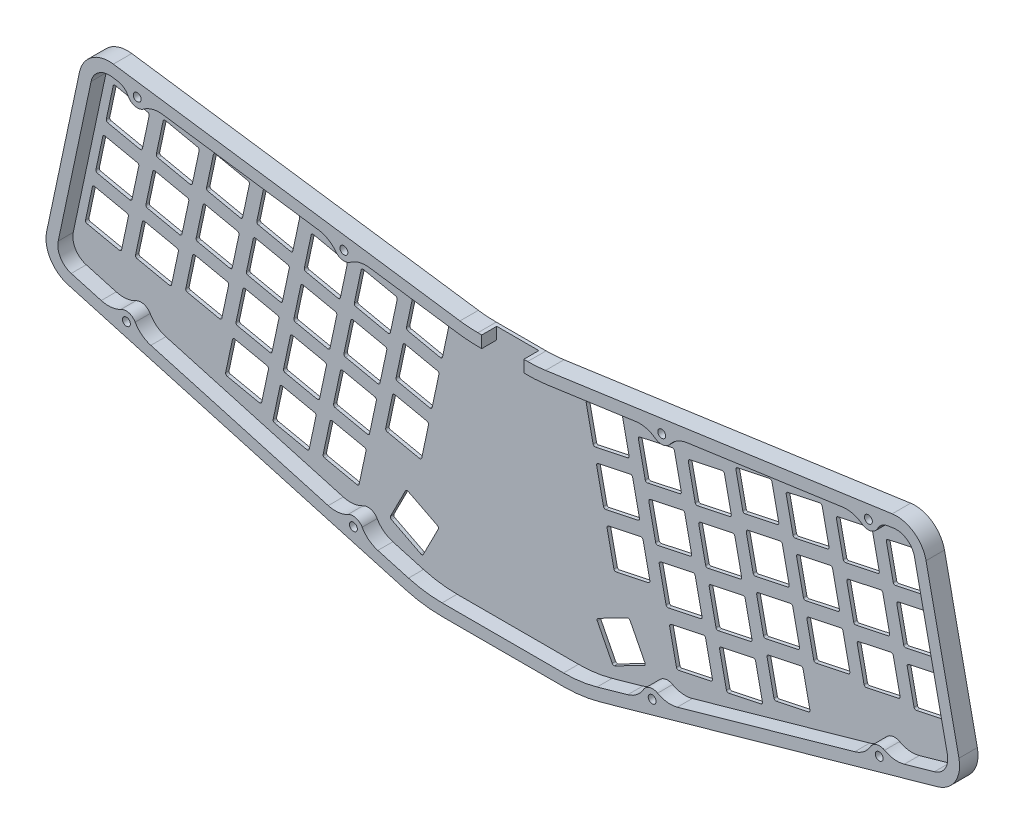
SolidWorks part; units mm, degrees
ref_plane "Front Plane" through (0, 0, 0) normal (0, 0, 1) x (1, 0, 0)
ref_plane "Top Plane" through (0, 0, 0) normal (0, 1, 0) x (1, 0, 0)
ref_plane "Right Plane" through (0, 0, 0) normal (1, 0, 0) x (0, 0, -1)
sketch "Model" plane through (0, 0, 0) normal (0, 0, 1) x (1, 0, 0)
  line L0 (7.1929, 63.9009) -> (19.4198, 61.302)
  line L1 (19.9974, 60.4125) -> (17.3986, 48.1856)
  line L2 (16.509, 47.6079) -> (4.2822, 50.2068)
  line L3 (3.7045, 51.0964) -> (6.3034, 63.3232)
  line L4 (3.2426, 45.3161) -> (15.4694, 42.7172)
  line L5 (16.0471, 41.8276) -> (13.4482, 29.6008)
  line L6 (12.5587, 29.0231) -> (0.3318, 31.622)
  line L7 (-0.2458, 32.5116) -> (2.3531, 44.7384)
  line L8 (-0.7077, 26.7313) -> (11.5191, 24.1324)
  line L9 (12.0968, 23.2428) -> (9.4979, 11.016)
  line L10 (8.6084, 10.4383) -> (-3.6185, 13.0372)
  line L11 (-4.1962, 13.9268) -> (-1.5973, 26.1536)
  line L12 (26.1936, 61.9069) -> (38.4204, 59.308)
  line L13 (38.9981, 58.4184) -> (36.3992, 46.1916)
  line L14 (35.5096, 45.6139) -> (23.2828, 48.2128)
  line L15 (22.7051, 49.1023) -> (25.304, 61.3292)
  line L16 (22.2432, 43.3221) -> (34.4701, 40.7232)
  line L17 (35.0478, 39.8336) -> (32.4489, 27.6068)
  line L18 (31.5593, 27.0291) -> (19.3325, 29.628)
  line L19 (18.7548, 30.5175) -> (21.3537, 42.7444)
  line L20 (18.2929, 24.7373) -> (30.5198, 22.1384)
  line L21 (31.0974, 21.2488) -> (28.4985, 9.022)
  line L22 (27.609, 8.4443) -> (15.3821, 11.0432)
  line L23 (14.8045, 11.9327) -> (17.4034, 24.1596)
  line L24 (45.2981, 60.4019) -> (57.525, 57.803)
  line L25 (58.1027, 56.9135) -> (55.5038, 44.6866)
  line L26 (54.6142, 44.109) -> (42.3874, 46.7078)
  line L27 (41.8097, 47.5974) -> (44.4086, 59.8242)
  line L28 (41.3478, 41.8171) -> (53.5747, 39.2182)
  line L29 (54.1523, 38.3287) -> (51.5534, 26.1018)
  line L30 (50.6639, 25.5241) -> (38.4371, 28.123)
  line L31 (37.8594, 29.0126) -> (40.4583, 41.2394)
  line L32 (37.3975, 23.2323) -> (49.6243, 20.6334)
  line L33 (50.202, 19.7439) -> (47.6031, 7.517)
  line L34 (46.7136, 6.9393) -> (34.4867, 9.5382)
  line L35 (33.9091, 10.4278) -> (36.5079, 22.6546)
  line L36 (64.4027, 58.897) -> (76.6296, 56.2981)
  line L37 (77.2072, 55.4085) -> (74.6083, 43.1817)
  line L38 (73.7188, 42.604) -> (61.492, 45.2029)
  line L39 (60.9143, 46.0924) -> (63.5132, 58.3193)
  line L40 (60.4524, 40.3122) -> (72.6792, 37.7133)
  line L41 (73.2569, 36.8237) -> (70.658, 24.5969)
  line L42 (69.7685, 24.0192) -> (57.5416, 26.6181)
  line L43 (56.964, 27.5076) -> (59.5629, 39.7345)
  line L44 (56.5021, 21.7274) -> (68.7289, 19.1285)
  line L45 (69.3066, 18.2389) -> (66.7077, 6.0121)
  line L46 (65.8182, 5.4344) -> (53.5913, 8.0333)
  line L47 (53.0136, 8.9228) -> (55.6125, 21.1497)
  line L48 (52.5518, 3.1425) -> (64.7786, 0.5437)
  line L49 (65.3563, -0.3459) -> (62.7574, -12.5727)
  line L50 (61.8678, -13.1504) -> (49.641, -10.5515)
  line L51 (49.0633, -9.662) -> (51.6622, 2.5649)
  line L52 (82.4677, 52.5013) -> (94.6946, 49.9024)
  line L53 (95.2723, 49.0128) -> (92.6734, 36.786)
  line L54 (91.7838, 36.2083) -> (79.557, 38.8072)
  line L55 (78.9793, 39.6967) -> (81.5782, 51.9236)
  line L56 (78.5174, 33.9165) -> (90.7443, 31.3176)
  line L57 (91.3219, 30.428) -> (88.723, 18.2012)
  line L58 (87.8335, 17.6235) -> (75.6067, 20.2224)
  line L59 (75.029, 21.1119) -> (77.6279, 33.3388)
  line L60 (74.5671, 15.3317) -> (86.7939, 12.7328)
  line L61 (87.3716, 11.8432) -> (84.7727, -0.3836)
  line L62 (83.8832, -0.9613) -> (71.6563, 1.6376)
  line L63 (71.0787, 2.5271) -> (73.6776, 14.754)
  line L64 (101.4684, 50.5072) -> (113.6952, 47.9083)
  line L65 (114.2729, 47.0188) -> (111.674, 34.792)
  line L66 (110.7845, 34.2143) -> (98.5576, 36.8132)
  line L67 (97.9799, 37.7027) -> (100.5788, 49.9296)
  line L68 (97.5181, 31.9224) -> (109.7449, 29.3235)
  line L69 (110.3226, 28.434) -> (107.7237, 16.2072)
  line L70 (106.8341, 15.6295) -> (94.6073, 18.2284)
  line L71 (94.0296, 19.1179) -> (96.6285, 31.3448)
  line L72 (93.5677, 13.3376) -> (105.7946, 10.7387)
  line L73 (106.3723, 9.8492) -> (103.7734, -2.3777)
  line L74 (102.8838, -2.9553) -> (90.657, -0.3564)
  line L75 (90.0793, 0.5331) -> (92.6782, 12.76)
  line L76 (134.1052, 48.9374) -> (131.5063, 36.7105)
  line L77 (130.6167, 36.1328) -> (118.3899, 38.7317)
  line L78 (117.8122, 39.6213) -> (120.4111, 51.8481)
  line L79 (117.3503, 33.841) -> (129.5772, 31.2421)
  line L80 (130.1548, 30.3526) -> (127.556, 18.1257)
  line L81 (126.6664, 17.548) -> (114.4396, 20.1469)
  line L82 (113.8619, 21.0365) -> (116.4608, 33.2633)
  line L83 (113.4, 15.2562) -> (125.6268, 12.6573)
  line L84 (126.2045, 11.7678) -> (123.6056, -0.4591)
  line L85 (122.7161, -1.0368) -> (110.4892, 1.5621)
  line L86 (109.9116, 2.4517) -> (112.5105, 14.6785)
  line L87 (70.6168, -3.2531) -> (82.8436, -5.852)
  line L88 (83.4213, -6.7416) -> (80.8224, -18.9684)
  line L89 (79.9329, -19.5461) -> (67.706, -16.9472)
  line L90 (67.1283, -16.0577) -> (69.7272, -3.8308)
  line L91 (89.6174, -5.2472) -> (101.8443, -7.8461)
  line L92 (102.4219, -8.7356) -> (99.823, -20.9625)
  line L93 (98.9335, -21.5401) -> (86.7066, -18.9412)
  line L94 (86.129, -18.0517) -> (88.7279, -5.8248)
  line L95 (117.654, -29.3648) -> (112.0852, -26.5274)
  line L96 (111.7574, -25.5186) -> (117.4323, -14.381)
  line L97 (118.4411, -14.0533) -> (129.5787, -19.7282)
  line L98 (129.9064, -20.7369) -> (124.2315, -31.8745)
  line L99 (123.2228, -32.2023) -> (117.654, -29.3648)
  line L100 (112.629, -33.5493) -> (124.2783, -36.8388)
  line L101 (137.0504, -38.6074) -> (160.1264, -38.6074)
  line L102 (160.1264, -38.6074) -> (183.2025, -38.6074)
  line L103 (195.9746, -36.8388) -> (207.6239, -33.5493)
  line L104 (226.4824, -28.2242) -> (271.949, -15.3856)
  line L105 (271.949, -15.3856) -> (293.9202, -9.1816)
  line L106 (210.7632, 57.9332) -> (177.0346, 53.1572)
  line L107 (169.604, 52.6338) -> (150.6488, 52.6338)
  line L108 (143.2182, 53.1572) -> (109.4896, 57.9332)
  line L109 (90.0873, 60.6806) -> (30.9176, 69.0589)
  line L110 (289.3352, 69.0589) -> (230.1656, 60.6806)
  line L111 (26.3327, -9.1816) -> (48.3039, -15.3856)
  line L112 (48.3039, -15.3856) -> (93.7705, -28.2242)
  line L113 (312.7787, -3.8564) -> (324.1811, -0.6367)
  line L114 (-2.1254, 39.3007) -> (3.622, 66.34)
  line L115 (-2.1254, 39.3007) -> (-8.8731, 7.5553)
  line L116 (13.8071, 71.4818) -> (11.4504, 71.8155)
  line L117 (-3.9283, -0.6367) -> (7.4742, -3.8564)
  line L118 (306.4458, 71.4818) -> (308.8024, 71.8155)
  line L119 (322.3782, 39.3007) -> (329.1259, 7.5553)
  line L120 (322.3782, 39.3007) -> (316.6308, 66.34)
  line L121 (121.3006, 52.4258) -> (133.5275, 49.8269)
  line L122 (313.0599, 63.9009) -> (300.8331, 61.302)
  line L123 (300.2554, 60.4125) -> (302.8543, 48.1856)
  line L124 (303.7438, 47.6079) -> (315.9707, 50.2068)
  line L125 (316.5483, 51.0964) -> (313.9494, 63.3232)
  line L126 (317.0102, 45.3161) -> (304.7834, 42.7172)
  line L127 (304.2057, 41.8276) -> (306.8046, 29.6008)
  line L128 (307.6941, 29.0231) -> (319.921, 31.622)
  line L129 (320.4987, 32.5116) -> (317.8998, 44.7384)
  line L130 (320.9605, 26.7313) -> (308.7337, 24.1324)
  line L131 (308.156, 23.2428) -> (310.7549, 11.016)
  line L132 (311.6445, 10.4383) -> (323.8713, 13.0372)
  line L133 (324.449, 13.9268) -> (321.8501, 26.1536)
  line L134 (294.0593, 61.9069) -> (281.8324, 59.308)
  line L135 (281.2548, 58.4184) -> (283.8536, 46.1916)
  line L136 (284.7432, 45.6139) -> (296.97, 48.2128)
  line L137 (297.5477, 49.1023) -> (294.9488, 61.3292)
  line L138 (298.0096, 43.3221) -> (285.7828, 40.7232)
  line L139 (285.2051, 39.8336) -> (287.804, 27.6068)
  line L140 (288.6935, 27.0291) -> (300.9204, 29.628)
  line L141 (301.498, 30.5175) -> (298.8991, 42.7444)
  line L142 (301.9599, 24.7373) -> (289.7331, 22.1384)
  line L143 (289.1554, 21.2488) -> (291.7543, 9.022)
  line L144 (292.6438, 8.4443) -> (304.8707, 11.0432)
  line L145 (305.4484, 11.9327) -> (302.8495, 24.1596)
  line L146 (274.9547, 60.4019) -> (262.7278, 57.803)
  line L147 (262.1502, 56.9135) -> (264.7491, 44.6866)
  line L148 (265.6386, 44.109) -> (277.8655, 46.7078)
  line L149 (278.4431, 47.5974) -> (275.8442, 59.8242)
  line L150 (278.905, 41.8171) -> (266.6782, 39.2182)
  line L151 (266.1005, 38.3287) -> (268.6994, 26.1018)
  line L152 (269.5889, 25.5241) -> (281.8158, 28.123)
  line L153 (282.3935, 29.0126) -> (279.7946, 41.2394)
  line L154 (282.8553, 23.2323) -> (270.6285, 20.6334)
  line L155 (270.0508, 19.7439) -> (272.6497, 7.517)
  line L156 (273.5393, 6.9393) -> (285.7661, 9.5382)
  line L157 (286.3438, 10.4278) -> (283.7449, 22.6546)
  line L158 (255.8501, 58.897) -> (243.6233, 56.2981)
  line L159 (243.0456, 55.4085) -> (245.6445, 43.1817)
  line L160 (246.534, 42.604) -> (258.7609, 45.2029)
  line L161 (259.3385, 46.0924) -> (256.7397, 58.3193)
  line L162 (259.8004, 40.3122) -> (247.5736, 37.7133)
  line L163 (246.9959, 36.8237) -> (249.5948, 24.5969)
  line L164 (250.4843, 24.0192) -> (262.7112, 26.6181)
  line L165 (263.2889, 27.5076) -> (260.69, 39.7345)
  line L166 (263.7508, 21.7274) -> (251.5239, 19.1285)
  line L167 (250.9462, 18.2389) -> (253.5451, 6.0121)
  line L168 (254.4347, 5.4344) -> (266.6615, 8.0333)
  line L169 (267.2392, 8.9228) -> (264.6403, 21.1497)
  line L170 (267.7011, 3.1425) -> (255.4742, 0.5437)
  line L171 (254.8966, -0.3459) -> (257.4954, -12.5727)
  line L172 (258.385, -13.1504) -> (270.6118, -10.5515)
  line L173 (271.1895, -9.662) -> (268.5906, 2.5649)
  line L174 (237.7851, 52.5013) -> (225.5582, 49.9024)
  line L175 (224.9806, 49.0128) -> (227.5795, 36.786)
  line L176 (228.469, 36.2083) -> (240.6958, 38.8072)
  line L177 (241.2735, 39.6967) -> (238.6746, 51.9236)
  line L178 (241.7354, 33.9165) -> (229.5086, 31.3176)
  line L179 (228.9309, 30.428) -> (231.5298, 18.2012)
  line L180 (232.4193, 17.6235) -> (244.6462, 20.2224)
  line L181 (245.2238, 21.1119) -> (242.6249, 33.3388)
  line L182 (245.6857, 15.3317) -> (233.4589, 12.7328)
  line L183 (232.8812, 11.8432) -> (235.4801, -0.3836)
  line L184 (236.3696, -0.9613) -> (248.5965, 1.6376)
  line L185 (249.1742, 2.5271) -> (246.5753, 14.754)
  line L186 (218.7845, 50.5072) -> (206.5576, 47.9083)
  line L187 (205.9799, 47.0188) -> (208.5788, 34.792)
  line L188 (209.4684, 34.2143) -> (221.6952, 36.8132)
  line L189 (222.2729, 37.7027) -> (219.674, 49.9296)
  line L190 (222.7348, 31.9224) -> (210.5079, 29.3235)
  line L191 (209.9303, 28.434) -> (212.5292, 16.2072)
  line L192 (213.4187, 15.6295) -> (225.6455, 18.2284)
  line L193 (226.2232, 19.1179) -> (223.6243, 31.3448)
  line L194 (226.6851, 13.3376) -> (214.4583, 10.7387)
  line L195 (213.8806, 9.8492) -> (216.4795, -2.3777)
  line L196 (217.369, -2.9553) -> (229.5959, -0.3564)
  line L197 (230.1735, 0.5331) -> (227.5746, 12.76)
  line L198 (186.1477, 48.9374) -> (188.7466, 36.7105)
  line L199 (189.6361, 36.1328) -> (201.8629, 38.7317)
  line L200 (202.4406, 39.6213) -> (199.8417, 51.8481)
  line L201 (202.9025, 33.841) -> (190.6757, 31.2421)
  line L202 (190.098, 30.3526) -> (192.6969, 18.1257)
  line L203 (193.5864, 17.548) -> (205.8133, 20.1469)
  line L204 (206.3909, 21.0365) -> (203.792, 33.2633)
  line L205 (206.8528, 15.2562) -> (194.626, 12.6573)
  line L206 (194.0483, 11.7678) -> (196.6472, -0.4591)
  line L207 (197.5367, -1.0368) -> (209.7636, 1.5621)
  line L208 (210.3413, 2.4517) -> (207.7424, 14.6785)
  line L209 (249.636, -3.2531) -> (237.4092, -5.852)
  line L210 (236.8315, -6.7416) -> (239.4304, -18.9684)
  line L211 (240.32, -19.5461) -> (252.5468, -16.9472)
  line L212 (253.1245, -16.0577) -> (250.5256, -3.8308)
  line L213 (230.6354, -5.2472) -> (218.4086, -7.8461)
  line L214 (217.8309, -8.7356) -> (220.4298, -20.9625)
  line L215 (221.3193, -21.5401) -> (233.5462, -18.9412)
  line L216 (234.1239, -18.0517) -> (231.525, -5.8248)
  line L217 (202.5988, -29.3648) -> (208.1676, -26.5274)
  line L218 (208.4954, -25.5186) -> (202.8205, -14.381)
  line L219 (201.8118, -14.0533) -> (190.6742, -19.7282)
  line L220 (190.3464, -20.7369) -> (196.0213, -31.8745)
  line L221 (197.03, -32.2023) -> (202.5988, -29.3648)
  line L222 (198.9522, 52.4258) -> (186.7253, 49.8269)
  line L223 (169.604, 55.6338) -> (150.6488, 55.6338)
  line L224 (143.6388, 56.1276) -> (11.8711, 74.7858)
  line L225 (0.6876, 66.9637) -> (-5.0598, 39.9244)
  line L226 (-5.0598, 39.9244) -> (-11.8075, 8.179)
  line L227 (-4.7435, -3.5238) -> (47.4886, -18.2727)
  line L228 (47.4886, -18.2727) -> (123.463, -39.7259)
  line L229 (137.0504, -41.6074) -> (160.1264, -41.6074)
  line L230 (160.1264, -41.6074) -> (183.2025, -41.6074)
  line L231 (196.7898, -39.7259) -> (272.7642, -18.2727)
  line L232 (272.7642, -18.2727) -> (324.9963, -3.5238)
  line L233 (332.0603, 8.179) -> (325.3126, 39.9244)
  line L234 (325.3126, 39.9244) -> (319.5653, 66.9637)
  line L235 (308.3818, 74.7858) -> (176.614, 56.1276)
  line L236 (169.604, 57.1338) -> (150.6488, 57.1338)
  line L237 (143.8491, 57.6128) -> (12.0814, 76.271)
  line L238 (-0.7797, 67.2756) -> (-6.527, 40.2363)
  line L239 (-6.527, 40.2363) -> (-13.2747, 8.4909)
  line L240 (-5.1511, -4.9673) -> (47.081, -19.7163)
  line L241 (47.081, -19.7163) -> (123.0554, -41.1694)
  line L242 (137.0504, -43.1074) -> (160.1264, -43.1074)
  line L243 (160.1264, -43.1074) -> (183.2025, -43.1074)
  line L244 (197.1974, -41.1694) -> (273.1718, -19.7163)
  line L245 (273.1718, -19.7163) -> (325.404, -4.9673)
  line L246 (333.5276, 8.4909) -> (326.7799, 40.2363)
  line L247 (326.7799, 40.2363) -> (321.0325, 67.2756)
  line L248 (308.1715, 76.271) -> (176.4037, 57.6128)
  arc A0 (106.6702, -28.8979) -> (101.2821, -27.3764) centre (103.1997, -30.8868) ccw
  arc A1 (93.7705, -28.2242) -> (101.2821, -27.3764) centre (96.4879, -18.6005) ccw
  arc A2 (106.6702, -28.8979) -> (112.629, -33.5493) centre (115.3464, -23.9256) ccw
  circle A3 centre (103.3356, -30.4056) radius 1.5
  arc A4 (207.6239, -33.5493) -> (213.5826, -28.8979) centre (204.9064, -23.9256) ccw
  arc A5 (218.9708, -27.3764) -> (226.4824, -28.2242) centre (223.7649, -18.6005) ccw
  arc A6 (218.9708, -27.3764) -> (213.5826, -28.8979) centre (217.0531, -30.8868) ccw
  circle A7 centre (216.9173, -30.4056) radius 1.5
  arc A8 (218.0932, 56.0855) -> (223.6367, 56.8704) centre (220.4644, 59.3069) ccw
  arc A9 (96.6161, 56.8704) -> (102.1596, 56.0855) centre (99.7884, 59.3069) ccw
  arc A10 (109.4896, 57.9332) -> (102.1596, 56.0855) centre (108.0876, 48.032) ccw
  arc A11 (96.6161, 56.8704) -> (90.0873, 60.6806) centre (88.6852, 50.7793) ccw
  arc A12 (218.0932, 56.0855) -> (210.7632, 57.9332) centre (212.1652, 48.032) ccw
  arc A13 (230.1656, 60.6806) -> (223.6367, 56.8704) centre (231.5676, 50.7793) ccw
  circle A14 centre (99.7183, 58.8118) radius 1.5
  circle A15 centre (220.5345, 58.8118) radius 1.5
  arc A16 (305.2671, -3.0086) -> (299.8789, -4.5301) centre (303.3494, -6.519) ccw
  arc A17 (20.3739, -4.5301) -> (14.9858, -3.0086) centre (16.9034, -6.519) ccw
  arc A18 (20.3739, -4.5301) -> (26.3327, -9.1816) centre (29.0501, 0.4421) ccw
  arc A19 (305.2671, -3.0086) -> (312.7787, -3.8564) centre (310.0612, 5.7673) ccw
  arc A20 (293.9202, -9.1816) -> (299.8789, -4.5301) centre (291.2027, 0.4421) ccw
  arc A21 (7.4742, -3.8564) -> (14.9858, -3.0086) centre (10.1916, 5.7673) ccw
  circle A22 centre (17.0393, -6.0378) radius 1.5
  circle A23 centre (303.2135, -6.0378) radius 1.5
  arc A24 (-8.8731, 7.5553) -> (-3.9283, -0.6367) centre (-2.026, 6.0999) ccw
  arc A25 (11.4504, 71.8155) -> (3.622, 66.34) centre (10.469, 64.8846) ccw
  arc A26 (316.6308, 66.34) -> (308.8024, 71.8155) centre (309.7838, 64.8846) ccw
  arc A27 (324.1811, -0.6367) -> (329.1259, 7.5553) centre (322.2789, 6.0999) ccw
  arc A28 (296.6652, 67.2112) -> (302.641, 68.6986) centre (299.0364, 70.4326) ccw
  arc A29 (17.6118, 68.6986) -> (23.5876, 67.2112) centre (21.2165, 70.4326) ccw
  arc A30 (30.9176, 69.0589) -> (23.5876, 67.2112) centre (29.5156, 59.1577) ccw
  arc A31 (17.6118, 68.6986) -> (13.8071, 71.4818) centre (13.106, 66.5312) ccw
  arc A32 (306.4458, 71.4818) -> (302.641, 68.6986) centre (307.1468, 66.5312) ccw
  arc A33 (296.6652, 67.2112) -> (289.3352, 69.0589) centre (290.7372, 59.1577) ccw
  circle A34 centre (299.1065, 69.9376) radius 1.5
  circle A35 centre (21.1464, 69.9376) radius 1.5
  arc A36 (3.7045, 51.0964) -> (4.2822, 50.2068) centre (4.4381, 50.9404) ccw
  arc A37 (7.1929, 63.9009) -> (6.3034, 63.3232) centre (7.037, 63.1673) ccw
  arc A38 (19.9974, 60.4125) -> (19.4198, 61.302) centre (19.2638, 60.5684) ccw
  arc A39 (16.509, 47.6079) -> (17.3986, 48.1856) centre (16.6649, 48.3415) ccw
  arc A40 (3.2426, 45.3161) -> (2.3531, 44.7384) centre (3.0867, 44.5825) ccw
  arc A41 (-0.2458, 32.5116) -> (0.3318, 31.622) centre (0.4878, 32.3556) ccw
  arc A42 (12.5587, 29.0231) -> (13.4482, 29.6008) centre (12.7146, 29.7567) ccw
  arc A43 (16.0471, 41.8276) -> (15.4694, 42.7172) centre (15.3135, 41.9836) ccw
  arc A44 (-0.7077, 26.7313) -> (-1.5973, 26.1536) centre (-0.8637, 25.9977) ccw
  arc A45 (-4.1962, 13.9268) -> (-3.6185, 13.0372) centre (-3.4625, 13.7708) ccw
  arc A46 (8.6084, 10.4383) -> (9.4979, 11.016) centre (8.7643, 11.1719) ccw
  arc A47 (12.0968, 23.2428) -> (11.5191, 24.1324) centre (11.3632, 23.3988) ccw
  arc A48 (14.8045, 11.9327) -> (15.3821, 11.0432) centre (15.5381, 11.7768) ccw
  arc A49 (27.609, 8.4443) -> (28.4985, 9.022) centre (27.7649, 9.1779) ccw
  arc A50 (31.0974, 21.2488) -> (30.5198, 22.1384) centre (30.3638, 21.4048) ccw
  arc A51 (18.2929, 24.7373) -> (17.4034, 24.1596) centre (18.137, 24.0036) ccw
  arc A52 (18.7548, 30.5175) -> (19.3325, 29.628) centre (19.4884, 30.3616) ccw
  arc A53 (31.5593, 27.0291) -> (32.4489, 27.6068) centre (31.7152, 27.7627) ccw
  arc A54 (35.0478, 39.8336) -> (34.4701, 40.7232) centre (34.3141, 39.9896) ccw
  arc A55 (22.2432, 43.3221) -> (21.3537, 42.7444) centre (22.0873, 42.5885) ccw
  arc A56 (22.7051, 49.1023) -> (23.2828, 48.2128) centre (23.4387, 48.9464) ccw
  arc A57 (35.5096, 45.6139) -> (36.3992, 46.1916) centre (35.6656, 46.3475) ccw
  arc A58 (38.9981, 58.4184) -> (38.4204, 59.308) centre (38.2645, 58.5744) ccw
  arc A59 (26.1936, 61.9069) -> (25.304, 61.3292) centre (26.0376, 61.1733) ccw
  arc A60 (33.9091, 10.4278) -> (34.4867, 9.5382) centre (34.6427, 10.2718) ccw
  arc A61 (37.3975, 23.2323) -> (36.5079, 22.6546) centre (37.2416, 22.4987) ccw
  arc A62 (50.202, 19.7439) -> (49.6243, 20.6334) centre (49.4684, 19.8998) ccw
  arc A63 (46.7136, 6.9393) -> (47.6031, 7.517) centre (46.8695, 7.673) ccw
  arc A64 (50.6639, 25.5241) -> (51.5534, 26.1018) centre (50.8198, 26.2578) ccw
  arc A65 (37.8594, 29.0126) -> (38.4371, 28.123) centre (38.593, 28.8567) ccw
  arc A66 (41.3478, 41.8171) -> (40.4583, 41.2394) centre (41.1919, 41.0835) ccw
  arc A67 (54.1523, 38.3287) -> (53.5747, 39.2182) centre (53.4187, 38.4846) ccw
  arc A68 (54.6142, 44.109) -> (55.5038, 44.6866) centre (54.7702, 44.8426) ccw
  arc A69 (41.8097, 47.5974) -> (42.3874, 46.7078) centre (42.5433, 47.4415) ccw
  arc A70 (45.2981, 60.4019) -> (44.4086, 59.8242) centre (45.1422, 59.6683) ccw
  arc A71 (58.1027, 56.9135) -> (57.525, 57.803) centre (57.369, 57.0694) ccw
  arc A72 (56.964, 27.5076) -> (57.5416, 26.6181) centre (57.6976, 27.3517) ccw
  arc A73 (60.4524, 40.3122) -> (59.5629, 39.7345) centre (60.2965, 39.5785) ccw
  arc A74 (73.2569, 36.8237) -> (72.6792, 37.7133) centre (72.5233, 36.9797) ccw
  arc A75 (69.7685, 24.0192) -> (70.658, 24.5969) centre (69.9244, 24.7528) ccw
  arc A76 (60.9143, 46.0924) -> (61.492, 45.2029) centre (61.6479, 45.9365) ccw
  arc A77 (73.7188, 42.604) -> (74.6083, 43.1817) centre (73.8747, 43.3376) ccw
  arc A78 (77.2072, 55.4085) -> (76.6296, 56.2981) centre (76.4736, 55.5645) ccw
  arc A79 (64.4027, 58.897) -> (63.5132, 58.3193) centre (64.2468, 58.1634) ccw
  arc A80 (53.0136, 8.9228) -> (53.5913, 8.0333) centre (53.7472, 8.7669) ccw
  arc A81 (56.5021, 21.7274) -> (55.6125, 21.1497) centre (56.3461, 20.9937) ccw
  arc A82 (69.3066, 18.2389) -> (68.7289, 19.1285) centre (68.573, 18.3948) ccw
  arc A83 (65.8182, 5.4344) -> (66.7077, 6.0121) centre (65.9741, 6.168) ccw
  arc A84 (49.0633, -9.662) -> (49.641, -10.5515) centre (49.7969, -9.8179) ccw
  arc A85 (52.5518, 3.1425) -> (51.6622, 2.5649) centre (52.3958, 2.4089) ccw
  arc A86 (65.3563, -0.3459) -> (64.7786, 0.5437) centre (64.6227, -0.19) ccw
  arc A87 (61.8678, -13.1504) -> (62.7574, -12.5727) centre (62.0238, -12.4168) ccw
  arc A88 (67.1283, -16.0577) -> (67.706, -16.9472) centre (67.8619, -16.2136) ccw
  arc A89 (70.6168, -3.2531) -> (69.7272, -3.8308) centre (70.4608, -3.9868) ccw
  arc A90 (83.4213, -6.7416) -> (82.8436, -5.852) centre (82.6877, -6.5856) ccw
  arc A91 (79.9329, -19.5461) -> (80.8224, -18.9684) centre (80.0888, -18.8125) ccw
  arc A92 (71.0787, 2.5271) -> (71.6563, 1.6376) centre (71.8123, 2.3712) ccw
  arc A93 (83.8832, -0.9613) -> (84.7727, -0.3836) centre (84.0391, -0.2277) ccw
  arc A94 (87.3716, 11.8432) -> (86.7939, 12.7328) centre (86.638, 11.9992) ccw
  arc A95 (74.5671, 15.3317) -> (73.6776, 14.754) centre (74.4112, 14.5981) ccw
  arc A96 (75.029, 21.1119) -> (75.6067, 20.2224) centre (75.7626, 20.956) ccw
  arc A97 (87.8335, 17.6235) -> (88.723, 18.2012) centre (87.9894, 18.3571) ccw
  arc A98 (91.3219, 30.428) -> (90.7443, 31.3176) centre (90.5883, 30.584) ccw
  arc A99 (78.5174, 33.9165) -> (77.6279, 33.3388) centre (78.3615, 33.1829) ccw
  arc A100 (78.9793, 39.6967) -> (79.557, 38.8072) centre (79.7129, 39.5408) ccw
  arc A101 (82.4677, 52.5013) -> (81.5782, 51.9236) centre (82.3118, 51.7677) ccw
  arc A102 (95.2723, 49.0128) -> (94.6946, 49.9024) centre (94.5387, 49.1688) ccw
  arc A103 (91.7838, 36.2083) -> (92.6734, 36.786) centre (91.9398, 36.9419) ccw
  arc A104 (97.9799, 37.7027) -> (98.5576, 36.8132) centre (98.7135, 37.5468) ccw
  arc A105 (101.4684, 50.5072) -> (100.5788, 49.9296) centre (101.3124, 49.7736) ccw
  arc A106 (114.2729, 47.0188) -> (113.6952, 47.9083) centre (113.5393, 47.1747) ccw
  arc A107 (110.7845, 34.2143) -> (111.674, 34.792) centre (110.9404, 34.9479) ccw
  arc A108 (97.5181, 31.9224) -> (96.6285, 31.3448) centre (97.3621, 31.1888) ccw
  arc A109 (110.3226, 28.434) -> (109.7449, 29.3235) centre (109.589, 28.5899) ccw
  arc A110 (106.8341, 15.6295) -> (107.7237, 16.2072) centre (106.9901, 16.3631) ccw
  arc A111 (94.0296, 19.1179) -> (94.6073, 18.2284) centre (94.7632, 18.962) ccw
  arc A112 (93.5677, 13.3376) -> (92.6782, 12.76) centre (93.4118, 12.604) ccw
  arc A113 (106.3723, 9.8492) -> (105.7946, 10.7387) centre (105.6386, 10.0051) ccw
  arc A114 (102.8838, -2.9553) -> (103.7734, -2.3777) centre (103.0397, -2.2217) ccw
  arc A115 (90.0793, 0.5331) -> (90.657, -0.3564) centre (90.8129, 0.3772) ccw
  arc A116 (89.6174, -5.2472) -> (88.7279, -5.8248) centre (89.4615, -5.9808) ccw
  arc A117 (102.4219, -8.7356) -> (101.8443, -7.8461) centre (101.6883, -8.5797) ccw
  arc A118 (98.9335, -21.5401) -> (99.823, -20.9625) centre (99.0894, -20.8065) ccw
  arc A119 (86.129, -18.0517) -> (86.7066, -18.9412) centre (86.8626, -18.2076) ccw
  arc A120 (111.7574, -25.5186) -> (112.0852, -26.5274) centre (112.4257, -25.8591) ccw
  arc A121 (118.4411, -14.0533) -> (117.4323, -14.381) centre (118.1006, -14.7215) ccw
  arc A122 (129.9064, -20.7369) -> (129.5787, -19.7282) centre (129.2382, -20.3964) ccw
  arc A123 (123.2228, -32.2023) -> (124.2315, -31.8745) centre (123.5633, -31.534) ccw
  arc A124 (109.9116, 2.4517) -> (110.4892, 1.5621) centre (110.6452, 2.2957) ccw
  arc A125 (122.7161, -1.0368) -> (123.6056, -0.4591) centre (122.872, -0.3032) ccw
  arc A126 (126.2045, 11.7678) -> (125.6268, 12.6573) centre (125.4709, 11.9237) ccw
  arc A127 (113.4, 15.2562) -> (112.5105, 14.6785) centre (113.2441, 14.5226) ccw
  arc A128 (113.8619, 21.0365) -> (114.4396, 20.1469) centre (114.5955, 20.8805) ccw
  arc A129 (126.6664, 17.548) -> (127.556, 18.1257) centre (126.8223, 18.2817) ccw
  arc A130 (130.1548, 30.3526) -> (129.5772, 31.2421) centre (129.4212, 30.5085) ccw
  arc A131 (117.3503, 33.841) -> (116.4608, 33.2633) centre (117.1944, 33.1074) ccw
  arc A132 (117.8122, 39.6213) -> (118.3899, 38.7317) centre (118.5458, 39.4654) ccw
  arc A133 (130.6167, 36.1328) -> (131.5063, 36.7105) centre (130.7727, 36.8665) ccw
  arc A134 (134.1052, 48.9374) -> (133.5275, 49.8269) centre (133.3716, 49.0933) ccw
  arc A135 (121.3006, 52.4258) -> (120.4111, 51.8481) centre (121.1447, 51.6922) ccw
  arc A136 (313.9494, 63.3232) -> (313.0599, 63.9009) centre (313.2158, 63.1673) ccw
  arc A137 (300.8331, 61.302) -> (300.2554, 60.4125) centre (300.989, 60.5684) ccw
  arc A138 (302.8543, 48.1856) -> (303.7438, 47.6079) centre (303.5879, 48.3415) ccw
  arc A139 (315.9707, 50.2068) -> (316.5483, 51.0964) centre (315.8147, 50.9404) ccw
  arc A140 (317.8998, 44.7384) -> (317.0102, 45.3161) centre (317.1662, 44.5825) ccw
  arc A141 (304.7834, 42.7172) -> (304.2057, 41.8276) centre (304.9393, 41.9836) ccw
  arc A142 (306.8046, 29.6008) -> (307.6941, 29.0231) centre (307.5382, 29.7567) ccw
  arc A143 (319.921, 31.622) -> (320.4987, 32.5116) centre (319.7651, 32.3556) ccw
  arc A144 (321.8501, 26.1536) -> (320.9605, 26.7313) centre (321.1165, 25.9977) ccw
  arc A145 (308.7337, 24.1324) -> (308.156, 23.2428) centre (308.8896, 23.3988) ccw
  arc A146 (310.7549, 11.016) -> (311.6445, 10.4383) centre (311.4885, 11.1719) ccw
  arc A147 (323.8713, 13.0372) -> (324.449, 13.9268) centre (323.7154, 13.7708) ccw
  arc A148 (294.9488, 61.3292) -> (294.0593, 61.9069) centre (294.2152, 61.1733) ccw
  arc A149 (281.8324, 59.308) -> (281.2548, 58.4184) centre (281.9884, 58.5744) ccw
  arc A150 (283.8536, 46.1916) -> (284.7432, 45.6139) centre (284.5873, 46.3475) ccw
  arc A151 (296.97, 48.2128) -> (297.5477, 49.1023) centre (296.8141, 48.9464) ccw
  arc A152 (298.8991, 42.7444) -> (298.0096, 43.3221) centre (298.1655, 42.5885) ccw
  arc A153 (285.7828, 40.7232) -> (285.2051, 39.8336) centre (285.9387, 39.9896) ccw
  arc A154 (287.804, 27.6068) -> (288.6935, 27.0291) centre (288.5376, 27.7627) ccw
  arc A155 (300.9204, 29.628) -> (301.498, 30.5175) centre (300.7644, 30.3616) ccw
  arc A156 (302.8495, 24.1596) -> (301.9599, 24.7373) centre (302.1159, 24.0036) ccw
  arc A157 (289.7331, 22.1384) -> (289.1554, 21.2488) centre (289.889, 21.4048) ccw
  arc A158 (291.7543, 9.022) -> (292.6438, 8.4443) centre (292.4879, 9.1779) ccw
  arc A159 (304.8707, 11.0432) -> (305.4484, 11.9327) centre (304.7147, 11.7768) ccw
  arc A160 (262.7278, 57.803) -> (262.1502, 56.9135) centre (262.8838, 57.0694) ccw
  arc A161 (275.8442, 59.8242) -> (274.9547, 60.4019) centre (275.1106, 59.6683) ccw
  arc A162 (264.7491, 44.6866) -> (265.6386, 44.109) centre (265.4827, 44.8426) ccw
  arc A163 (277.8655, 46.7078) -> (278.4431, 47.5974) centre (277.7095, 47.4415) ccw
  arc A164 (266.6782, 39.2182) -> (266.1005, 38.3287) centre (266.8341, 38.4846) ccw
  arc A165 (279.7946, 41.2394) -> (278.905, 41.8171) centre (279.0609, 41.0835) ccw
  arc A166 (268.6994, 26.1018) -> (269.5889, 25.5241) centre (269.433, 26.2578) ccw
  arc A167 (281.8158, 28.123) -> (282.3935, 29.0126) centre (281.6598, 28.8567) ccw
  arc A168 (270.6285, 20.6334) -> (270.0508, 19.7439) centre (270.7844, 19.8998) ccw
  arc A169 (283.7449, 22.6546) -> (282.8553, 23.2323) centre (283.0113, 22.4987) ccw
  arc A170 (272.6497, 7.517) -> (273.5393, 6.9393) centre (273.3833, 7.673) ccw
  arc A171 (285.7661, 9.5382) -> (286.3438, 10.4278) centre (285.6102, 10.2718) ccw
  arc A172 (256.7397, 58.3193) -> (255.8501, 58.897) centre (256.006, 58.1634) ccw
  arc A173 (243.6233, 56.2981) -> (243.0456, 55.4085) centre (243.7792, 55.5645) ccw
  arc A174 (245.6445, 43.1817) -> (246.534, 42.604) centre (246.3781, 43.3376) ccw
  arc A175 (258.7609, 45.2029) -> (259.3385, 46.0924) centre (258.6049, 45.9365) ccw
  arc A176 (247.5736, 37.7133) -> (246.9959, 36.8237) centre (247.7295, 36.9797) ccw
  arc A177 (260.69, 39.7345) -> (259.8004, 40.3122) centre (259.9564, 39.5785) ccw
  arc A178 (249.5948, 24.5969) -> (250.4843, 24.0192) centre (250.3284, 24.7528) ccw
  arc A179 (262.7112, 26.6181) -> (263.2889, 27.5076) centre (262.5553, 27.3517) ccw
  arc A180 (251.5239, 19.1285) -> (250.9462, 18.2389) centre (251.6798, 18.3948) ccw
  arc A181 (253.5451, 6.0121) -> (254.4347, 5.4344) centre (254.2787, 6.168) ccw
  arc A182 (264.6403, 21.1497) -> (263.7508, 21.7274) centre (263.9067, 20.9937) ccw
  arc A183 (266.6615, 8.0333) -> (267.2392, 8.9228) centre (266.5056, 8.7669) ccw
  arc A184 (255.4742, 0.5437) -> (254.8966, -0.3459) centre (255.6302, -0.19) ccw
  arc A185 (257.4954, -12.5727) -> (258.385, -13.1504) centre (258.2291, -12.4168) ccw
  arc A186 (268.5906, 2.5649) -> (267.7011, 3.1425) centre (267.857, 2.4089) ccw
  arc A187 (270.6118, -10.5515) -> (271.1895, -9.662) centre (270.4559, -9.8179) ccw
  arc A188 (225.5582, 49.9024) -> (224.9806, 49.0128) centre (225.7142, 49.1688) ccw
  arc A189 (238.6746, 51.9236) -> (237.7851, 52.5013) centre (237.941, 51.7677) ccw
  arc A190 (227.5795, 36.786) -> (228.469, 36.2083) centre (228.3131, 36.9419) ccw
  arc A191 (240.6958, 38.8072) -> (241.2735, 39.6967) centre (240.5399, 39.5408) ccw
  arc A192 (242.6249, 33.3388) -> (241.7354, 33.9165) centre (241.8913, 33.1829) ccw
  arc A193 (229.5086, 31.3176) -> (228.9309, 30.428) centre (229.6645, 30.584) ccw
  arc A194 (231.5298, 18.2012) -> (232.4193, 17.6235) centre (232.2634, 18.3571) ccw
  arc A195 (244.6462, 20.2224) -> (245.2238, 21.1119) centre (244.4902, 20.956) ccw
  arc A196 (246.5753, 14.754) -> (245.6857, 15.3317) centre (245.8417, 14.5981) ccw
  arc A197 (233.4589, 12.7328) -> (232.8812, 11.8432) centre (233.6148, 11.9992) ccw
  arc A198 (235.4801, -0.3836) -> (236.3696, -0.9613) centre (236.2137, -0.2277) ccw
  arc A199 (248.5965, 1.6376) -> (249.1742, 2.5271) centre (248.4406, 2.3712) ccw
  arc A200 (206.5576, 47.9083) -> (205.9799, 47.0188) centre (206.7135, 47.1747) ccw
  arc A201 (219.674, 49.9296) -> (218.7845, 50.5072) centre (218.9404, 49.7736) ccw
  arc A202 (208.5788, 34.792) -> (209.4684, 34.2143) centre (209.3124, 34.9479) ccw
  arc A203 (221.6952, 36.8132) -> (222.2729, 37.7027) centre (221.5393, 37.5468) ccw
  arc A204 (210.5079, 29.3235) -> (209.9303, 28.434) centre (210.6639, 28.5899) ccw
  arc A205 (223.6243, 31.3448) -> (222.7348, 31.9224) centre (222.8907, 31.1888) ccw
  arc A206 (212.5292, 16.2072) -> (213.4187, 15.6295) centre (213.2628, 16.3631) ccw
  arc A207 (225.6455, 18.2284) -> (226.2232, 19.1179) centre (225.4896, 18.962) ccw
  arc A208 (227.5746, 12.76) -> (226.6851, 13.3376) centre (226.841, 12.604) ccw
  arc A209 (216.4795, -2.3777) -> (217.369, -2.9553) centre (217.2131, -2.2217) ccw
  arc A210 (214.4583, 10.7387) -> (213.8806, 9.8492) centre (214.6142, 10.0051) ccw
  arc A211 (229.5959, -0.3564) -> (230.1735, 0.5331) centre (229.4399, 0.3772) ccw
  arc A212 (199.8417, 51.8481) -> (198.9522, 52.4258) centre (199.1081, 51.6922) ccw
  arc A213 (186.7253, 49.8269) -> (186.1477, 48.9374) centre (186.8813, 49.0933) ccw
  arc A214 (188.7466, 36.7105) -> (189.6361, 36.1328) centre (189.4802, 36.8665) ccw
  arc A215 (201.8629, 38.7317) -> (202.4406, 39.6213) centre (201.707, 39.4654) ccw
  arc A216 (203.792, 33.2633) -> (202.9025, 33.841) centre (203.0584, 33.1074) ccw
  arc A217 (190.6757, 31.2421) -> (190.098, 30.3526) centre (190.8316, 30.5085) ccw
  arc A218 (192.6969, 18.1257) -> (193.5864, 17.548) centre (193.4305, 18.2817) ccw
  arc A219 (205.8133, 20.1469) -> (206.3909, 21.0365) centre (205.6573, 20.8805) ccw
  arc A220 (207.7424, 14.6785) -> (206.8528, 15.2562) centre (207.0088, 14.5226) ccw
  arc A221 (194.626, 12.6573) -> (194.0483, 11.7678) centre (194.7819, 11.9237) ccw
  arc A222 (196.6472, -0.4591) -> (197.5367, -1.0368) centre (197.3808, -0.3032) ccw
  arc A223 (209.7636, 1.5621) -> (210.3413, 2.4517) centre (209.6077, 2.2957) ccw
  arc A224 (250.5256, -3.8308) -> (249.636, -3.2531) centre (249.792, -3.9868) ccw
  arc A225 (239.4304, -18.9684) -> (240.32, -19.5461) centre (240.164, -18.8125) ccw
  arc A226 (237.4092, -5.852) -> (236.8315, -6.7416) centre (237.5651, -6.5856) ccw
  arc A227 (252.5468, -16.9472) -> (253.1245, -16.0577) centre (252.3909, -16.2136) ccw
  arc A228 (218.4086, -7.8461) -> (217.8309, -8.7356) centre (218.5645, -8.5797) ccw
  arc A229 (231.525, -5.8248) -> (230.6354, -5.2472) centre (230.7914, -5.9808) ccw
  arc A230 (220.4298, -20.9625) -> (221.3193, -21.5401) centre (221.1634, -20.8065) ccw
  arc A231 (233.5462, -18.9412) -> (234.1239, -18.0517) centre (233.3903, -18.2076) ccw
  arc A232 (208.1676, -26.5274) -> (208.4954, -25.5186) centre (207.8271, -25.8591) ccw
  arc A233 (190.6742, -19.7282) -> (190.3464, -20.7369) centre (191.0147, -20.3964) ccw
  arc A234 (202.8205, -14.381) -> (201.8118, -14.0533) centre (202.1522, -14.7215) ccw
  arc A235 (196.0213, -31.8745) -> (197.03, -32.2023) centre (196.6895, -31.534) ccw
  arc A236 (124.2783, -36.8388) -> (137.0504, -38.6074) centre (137.0504, 8.3926) ccw
  arc A237 (183.2025, -38.6074) -> (195.9746, -36.8388) centre (183.2025, 8.3926) ccw
  arc A238 (169.604, 52.6338) -> (177.0346, 53.1572) centre (169.604, 105.6338) ccw
  arc A239 (143.2182, 53.1572) -> (150.6488, 52.6338) centre (150.6488, 105.6338) ccw
  arc A240 (169.604, 55.6338) -> (176.614, 56.1276) centre (169.604, 105.6338) ccw
  arc A241 (143.6388, 56.1276) -> (150.6488, 55.6338) centre (150.6488, 105.6338) ccw
  arc A242 (11.8711, 74.7858) -> (0.6876, 66.9637) centre (10.469, 64.8846) ccw
  arc A243 (-11.8075, 8.179) -> (-4.7435, -3.5238) centre (-2.026, 6.0999) ccw
  arc A244 (123.463, -39.7259) -> (137.0504, -41.6074) centre (137.0504, 8.3926) ccw
  arc A245 (183.2025, -41.6074) -> (196.7898, -39.7259) centre (183.2025, 8.3926) ccw
  arc A246 (324.9963, -3.5238) -> (332.0603, 8.179) centre (322.2789, 6.0999) ccw
  arc A247 (319.5653, 66.9637) -> (308.3818, 74.7858) centre (309.7838, 64.8846) ccw
  arc A248 (169.604, 57.1338) -> (176.4037, 57.6128) centre (169.604, 105.6338) ccw
  arc A249 (143.8491, 57.6128) -> (150.6488, 57.1338) centre (150.6488, 105.6338) ccw
  arc A250 (12.0814, 76.271) -> (-0.7797, 67.2756) centre (10.469, 64.8846) ccw
  arc A251 (-13.2747, 8.4909) -> (-5.1511, -4.9673) centre (-2.026, 6.0999) ccw
  arc A252 (123.0554, -41.1694) -> (137.0504, -43.1074) centre (137.0504, 8.3926) ccw
  arc A253 (183.2025, -43.1074) -> (197.1974, -41.1694) centre (183.2025, 8.3926) ccw
  arc A254 (325.404, -4.9673) -> (333.5276, 8.4909) centre (322.2789, 6.0999) ccw
  arc A255 (321.0325, 67.2756) -> (308.1715, 76.271) centre (309.7838, 64.8846) ccw
extrude "Boss-Extrude1" add sketch "Model" along normal blind 7 contours L247 A255 L248 A248 L236 A249 L237 A250 L238 L239 A251 L240 L241 A252 L242 L243 A253 L244 L245 A254 L246 A247 L234 L233 A246 L232 L231 A245 L230 L229 A244 L228 L227 A243 L226 L225 A242 L224 A241 L223 A240 L235 | L234 A247 L235 A240 L223 A241 L224 A242 L225 L226 A243 L227 L228 A244 L229 L230 A245 L231 L232 A246 L233 L108 A239 L107 A238 L106 A12 A8 A13 L110 A33 A28 A32 L118 A26 L120 L119 A27 L113 A19 A16 A20 L105 L104 A5 A6 A4 L103 A237 L102 region at (173.1432, 55.3948, 0) region at (173.0381, 56.8873, 0)
extrude "Boss-Extrude2" add sketch "Model<3>" along normal blind 1.3 contours A239 L108 A10 A9 A11 L109 A30 A29 A31 L116 A25 L114 L115 A24 L117 A21 A17 A18 L111 L112 A1 A0 A2 L100 A236 L101 L102 A237 L103 A4 A6 A5 L104 L105 A20 A16 A19 L113 A27 L119 L120 A26 L118 A32 A28 A33 L110 A13 A8 A12 L106 region at (160.1264, 15.6084, 0)
sketch "Model<3>" plane through (0, 0, 0) normal (0, 0, 1) x (1, 0, 0) same geometry as "Model"
extrude "Boss-Extrude3" add sketch "Model<4>" along normal blind 2 contours A22 | A3 | A14 | A7 | A15 | A34 | A23 | A35 region at (103.3356, -30.4056, 0) region at (216.9173, -30.4056, 0) region at (99.7183, 58.8118, 0) region at (220.5345, 58.8118, 0) region at (17.0393, -6.0378, 0) region at (303.2135, -6.0378, 0) region at (299.1065, 69.9376, 0)
sketch "Model<4>" plane through (0, 0, 0) normal (0, 0, 1) x (1, 0, 0) same geometry as "Model"
sketch "Sketch3" plane through (0, 57.1338, 0) normal (0, 1, 0) x (1, 0, 0)
  line L1 (169.604, -7) -> (150.6488, -7) construction
  line L2 (160.1264, -1.3) -> (168.1264, -1.3)
  line L3 (168.1264, -1.3) -> (168.1264, -7)
  line L4 (168.1264, -7) -> (160.1264, -7)
  line L5 (160.1264, -7) -> (152.1264, -7)
  line L6 (152.1264, -7) -> (152.1264, -1.3)
  line L7 (152.1264, -1.3) -> (160.1264, -1.3)
extrude "Cut-Extrude1" cut sketch "Sketch3" against normal blind 10
